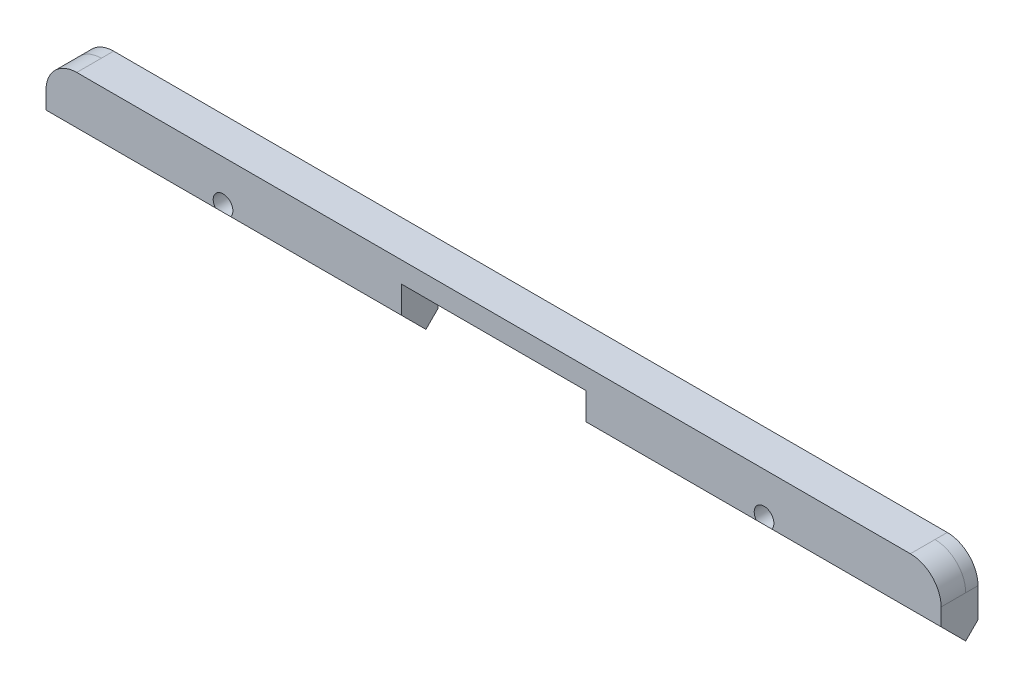
SolidWorks part; units mm, degrees
material "6061-T6 (SS)"
ref_plane "Front Plane" through (0, 0, 0) normal (0, 0, 1) x (1, 0, 0)
ref_plane "Top Plane" through (0, 0, 0) normal (0, 1, 0) x (1, 0, 0)
ref_plane "Right Plane" through (0, 0, 0) normal (1, 0, 0) x (0, 0, -1)
sketch "Sketch1" plane through (0, 0, 0) normal (1, 0, 0) x (0, 0, -1)
  line L0 (-3.0983, 0) -> (1.226, 0) construction
  line L1 (0, -3.2) -> (-2, -1.2)
  line L2 (0, -3.2) -> (0, 3.2)
  line L4 (-2, -1.2) -> (-2, 3.2)
  line L5 (-2, 3.2) -> (0, 3.2)
  dimension "D1" = 2
  dimension "D2" = 45
  dimension "D3" = 6.4
extrude "Boss-Extrude1" add sketch "Sketch1" along normal mid plane 72.8
fillet "Fillet3" radius 2.5 2 edges at (-36.4, 3.2, 1) (36.4, 3.2, 1)
sketch "Sketch5" plane through (-36.4, 0, 0) normal (-1, 0, 0) x (0, 0, 1)
  line L0 (0, -2.7) -> (2, -0.7)
  line L1 (0, -3.2) -> (0, 0.7) construction
  line L2 (2, 0.7) -> (2, -1.2) construction
  line L3 (2, -1.2) -> (0, -3.2) construction
  line L4 (2, -1.2) -> (2, -0.7)
  line L5 (2, -1.2) -> (0, -3.2)
  line L6 (0, -3.2) -> (0, -2.7)
  dimension "D1" = 0.5
extrude "Cut-Extrude5" cut sketch "Sketch5" against normal up to surface (72.8 mm away) up to face at (36.4, -0.75, 1)
sketch "Sketch7" plane through (-36.4, 0, 0) normal (-1, 0, 0) x (0, 0, 1)
  line L0 (0, -2.7) -> (-1, -1.7)
  line L1 (-1, -1.7) -> (-1, 3.2)
  line L2 (-1, 3.2) -> (0, 3.2)
  line L3 (0, 3.2) -> (0, -2.7)
  line L4 (0, 3.2) -> (2, 3.2) construction
  dimension "D1" = 45
  dimension "D2" = 3
extrude "Boss-Extrude2" add sketch "Sketch7" against normal up to surface (72.8 mm away) up to face at (36.4, -0.5, 1)
hole_wizard "M2x0.4 Tapped Hole1" positions "Sketch2" profile "Sketch3" tap size "M2x0.4" standard "ANSI Metric"
sketch "Sketch2" plane through (0, 0, 2) normal (0, 0, 1) x (1, 0, 0)
  circle A4 centre (-22, -0.2) radius 1.2 construction
  circle A5 centre (-22, -0.2) radius 1.2
  circle A6 centre (0, -0.2) radius 1.2 construction
  circle A7 centre (0, -0.2) radius 1.2
  circle A8 centre (22, -0.2) radius 1.2 construction
  circle A9 centre (22, -0.2) radius 1.2
  point P22 (-22, -0.2)
  point P25 (0, -0.2)
  point P28 (22, -0.2)
cosmetic thread "Hole Thread4" [suppressed] parameters "D1"=2, "D2"=2
cosmetic thread "Hole Thread6" [suppressed] parameters "D1"=2, "D2"=2
sketch "Sketch3" plane through (-22, -0.2, 2) normal (1, 0, 0) x (0, -1, 0)
  line L0 (0, 0) -> (0, 4.0807)
  line L1 (0, 4.0807) -> (0.8, 3.6)
  line L2 (0.8, 3.6) -> (0.8, 0)
  line L5 (0.8, 0) -> (0, 0)
  line L10 (0, 4.0807) -> (-0.8, 3.6) construction
  line L11 (0, -6.35) -> (0, 107.95) construction
  dimension "Tap Drill Dia." = 1.6
  dimension "Tap Drill Depth" = 3.6
  dimension "Drill Angle" = 118
cosmetic thread "Hole Thread7" parameters "D1"=2, "D2"=2
fillet "Fillet4" radius 2.5 2 edges at (-36.4, 3.2, -0.5) (36.4, 3.2, -0.5)
sketch "Sketch4" plane through (0, 0, 0) normal (0, 0, 1) x (1, 0, 0)
  line L1 (7.5, 1.5) -> (-7.5, 1.5)
  line L2 (7.5, 1.5) -> (7.5, -3.2)
  line L3 (7.5, -3.2) -> (-7.5, -3.2)
  line L4 (-7.5, 1.5) -> (-7.5, -3.2)
  line L5 (0, 7.7759) -> (0, -8.8374) construction
  line L8 (-7.5, -1.7) -> (-7.5, -0.7) construction
  dimension "D1" = 4.7
extrude "Cut-Extrude4" cut sketch "Sketch4" along normal mid plane 10
